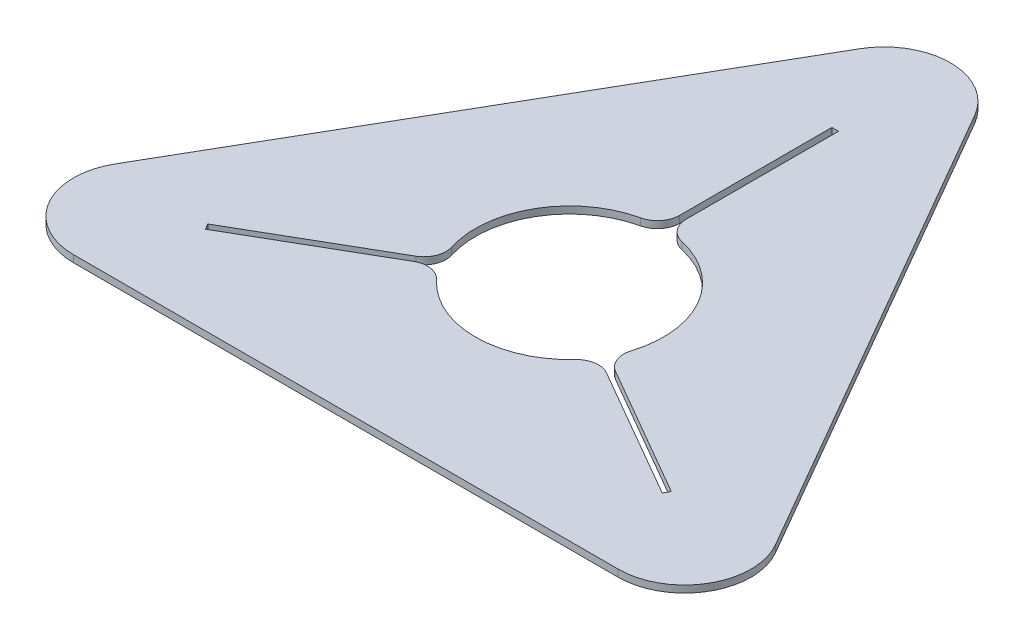
SolidWorks part; units mm, degrees
material "Beech"
ref_plane "Front Plane" through (0, 0, 0) normal (0, 0, 1) x (1, 0, 0)
ref_plane "Top Plane" through (0, 0, 0) normal (0, 1, 0) x (1, 0, 0)
ref_plane "Right Plane" through (0, 0, 0) normal (1, 0, 0) x (0, 0, -1)
sketch "Sketch1" plane through (0, 0, 0) normal (0, 1, 0) x (1, 0, 0)
  line L0 (0, 0) -> (-350, -606.2178)
  line L1 (-350, -606.2178) -> (350, -606.2178)
  line L2 (350, -606.2178) -> (0, 0)
extrude "Boss-Extrude1" add sketch "Sketch1" along normal blind 6.35
sketch "Sketch2" plane through (0, 6.35, 0) normal (0, 1, 0) x (1, 0, 0)
  circle A0 centre (0, -404.1452) radius 85
  dimension "D1" = 170
extrude "Cut-Extrude1" cut sketch "Sketch2" against normal blind 6.35
fillet "Fillet1" radius 60 3 edges at (0, 3.175, 0) (350, 3.175, 606.2178) (-350, 3.175, 606.2178)
sketch "Sketch3" plane through (0, 6.35, 0) normal (0, 1, 0) x (1, 0, 0)
  line L0 (27.4808, -416.5471) -> (24.4808, -421.7433)
  line L1 (-3, -374.1452) -> (3, -374.1452)
  line L2 (-3, -374.1452) -> (-3, -164.1452)
  line L3 (-3, -164.1452) -> (3, -164.1452)
  line L4 (3, -374.1452) -> (3, -164.1452)
  line L5 (27.4808, -416.5471) -> (209.3461, -521.5471)
  line L6 (209.3461, -521.5471) -> (206.3461, -526.7433)
  line L7 (24.4808, -421.7433) -> (206.3461, -526.7433)
  line L8 (-24.4808, -421.7433) -> (-27.4808, -416.5471)
  line L9 (-24.4808, -421.7433) -> (-206.3461, -526.7433)
  line L10 (-206.3461, -526.7433) -> (-209.3461, -521.5471)
  line L11 (-27.4808, -416.5471) -> (-209.3461, -521.5471)
  circle A0 centre (0, -404.1452) radius 85 construction
  point P4 (0, -374.1452)
  point P7 (0, 0)
  point P8 (0, 0)
  point P9 (0, 0)
  point P18 (0, -404.1452)
  dimension "D1" = 0
  dimension "D2" = 30
  dimension "D3" = 210
  dimension "D4" = 6
  dimension "D5" = 3
extrude "Cut-Extrude2" cut sketch "Sketch3" against normal blind 6.35
fillet "Fillet2" radius 20 6 edges at (-3, 3.175, 319.1981) (3, 3.175, 319.1981) (75.0663, 3.175, 444.0206) (72.0663, 3.175, 449.2168) (-72.0663, 3.175, 449.2168) (-75.0663, 3.175, 444.0206)
